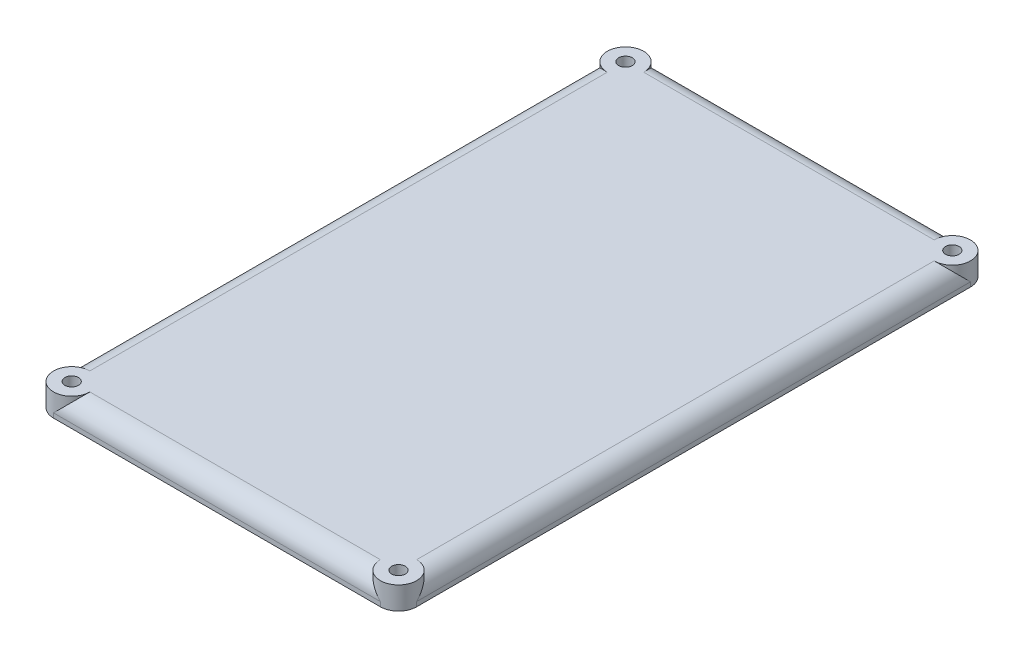
SolidWorks part; units mm, degrees
ref_plane "Front Plane" through (0, 0, 0) normal (0, 0, 1) x (1, 0, 0)
ref_plane "Top Plane" through (0, 0, 0) normal (0, 1, 0) x (1, 0, 0)
ref_plane "Right Plane" through (0, 0, 0) normal (1, 0, 0) x (0, 0, -1)
sketch "Sketch1" plane through (0, 0, 0) normal (0, 1, 0) x (1, 0, 0)
  line L1 (0, 0) -> (50.8, 0)
  line L2 (0, 0) -> (0, -82.55)
  line L3 (0, -82.55) -> (50.8, -82.55)
  line L4 (50.8, 0) -> (50.8, -82.55)
  dimension "D1" = 50.8
  dimension "D2" = 82.55
extrude "Boss-Extrude1" add sketch "Sketch1" along normal blind 3.175
fillet "Fillet1" radius 2.54 8 edges at (0, 1.5875, 0) (50.8, 1.5875, 0) (25.4, 3.175, 0) (50.8, 3.175, 41.275) (50.8, 1.5875, 82.55) (0, 1.5875, 82.55) (0, 3.175, 41.275) (25.4, 3.175, 82.55)
sketch "Sketch2" plane through (0, 3.175, 0) normal (0, 1, 0) x (1, 0, 0)
  circle A0 centre (48.26, -80.01) radius 2.54
  circle A1 centre (2.54, -80.01) radius 2.54
  circle A2 centre (2.54, -2.54) radius 2.54
  circle A3 centre (48.26, -2.54) radius 2.54
  arc A4 (50.8, -2.54) -> (48.26, 0) centre (48.26, -2.54) ccw construction
  arc A5 (48.26, -82.55) -> (50.8, -80.01) centre (48.26, -80.01) ccw construction
  arc A6 (0, -80.01) -> (2.54, -82.55) centre (2.54, -80.01) ccw construction
  arc A7 (2.54, 0) -> (0, -2.54) centre (2.54, -2.54) ccw construction
extrude "Cut-Extrude1" cut sketch "Sketch2" against normal through all
extrude "Boss-Extrude2" add sketch "Sketch2<2>" against normal blind 3.175
sketch "Sketch2<2>" plane through (0, 3.175, 0) normal (0, 1, 0) x (1, 0, 0) same geometry as "Sketch2"
sketch "Sketch3" plane through (0, 3.175, 0) normal (0, 1, 0) x (1, 0, 0)
  circle A0 centre (2.54, -2.54) radius 0.9525
  circle A1 centre (48.26, -2.54) radius 0.9525
  circle A2 centre (2.54, -80.01) radius 0.9525
  circle A3 centre (48.26, -80.01) radius 0.9525
  arc A4 (5.08, -2.54) -> (2.54, -5.08) centre (2.54, -2.54) ccw construction
  arc A5 (48.26, -5.08) -> (45.72, -2.54) centre (48.26, -2.54) ccw construction
  arc A6 (45.72, -80.01) -> (48.26, -77.47) centre (48.26, -80.01) ccw construction
  arc A7 (2.54, -77.47) -> (5.08, -80.01) centre (2.54, -80.01) ccw construction
  dimension "D1" = 1.905
extrude "Cut-Extrude2" cut sketch "Sketch3" against normal through all
